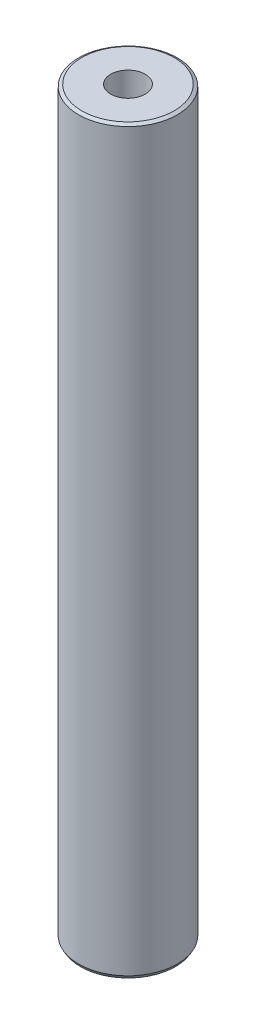
SolidWorks part; units mm, degrees
ref_plane "Front Plane" through (0, 0, 0) normal (0, 0, 1) x (1, 0, 0)
ref_plane "Top Plane" through (0, 0, 0) normal (0, 1, 0) x (1, 0, 0)
ref_plane "Right Plane" through (0, 0, 0) normal (1, 0, 0) x (0, 0, -1)
sketch "Sketch1" plane through (0, 0, 0) normal (0, 1, 0) x (1, 0, 0)
  circle A0 centre (0, 0) radius 40
  dimension "SHAFT_OD" = 80
extrude "Boss-Extrude1" add sketch "Sketch1" along normal blind 600
sketch "Sketch2" plane through (0, 0, 0) normal (0, 1, 0) x (1, 0, 0)
  circle A0 centre (0, 0) radius 13.9997
  dimension "BORE_D" = 27.9995
extrude "Cut-Extrude1" cut sketch "Sketch2" along normal through all
chamfer "Chamfer1" distance 1.4861 angle 60 2 edges at (0, 600, 40) (0, 0, 40) first distance on face at (0, 600, 40) first distance on face at (0, 0, 13.9997)
